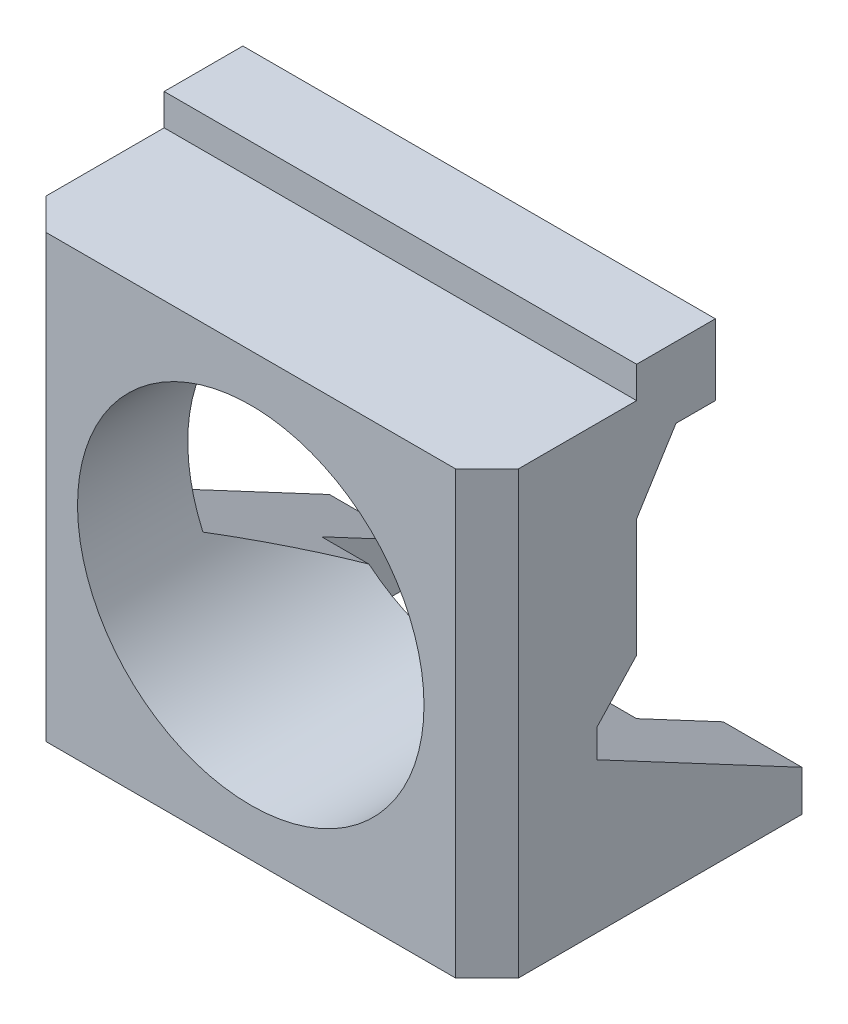
SolidWorks part; units mm, degrees
ref_plane "Front Plane" through (0, 0, 0) normal (0, 0, 1) x (1, 0, 0)
ref_plane "Top Plane" through (0, 0, 0) normal (0, 1, 0) x (1, 0, 0)
ref_plane "Right Plane" through (0, 0, 0) normal (1, 0, 0) x (0, 0, -1)
sketch "Sketch1" plane through (0, 0, 0) normal (0, 0, 1) x (1, 0, 0)
  line L1 (-15, 14) -> (15, 14)
  line L2 (-15, 14) -> (-15, -14)
  line L3 (-15, -14) -> (15, -14)
  line L4 (15, 14) -> (15, -14)
  line L5 (-15, 14) -> (15, -14) construction
  line L6 (-15, -14) -> (15, 14) construction
  circle A0 centre (0, 0) radius 11
  dimension "D1" = 22
  dimension "D2" = 30
  dimension "D3" = 28
extrude "Boss-Extrude1" add sketch "Sketch1" along normal blind 7
sketch "Sketch2" plane through (0, 0, 0) normal (0, 0, -1) x (-1, 0, 0)
  line L0 (0, 0) -> (0, -50000) construction
  line L1 (-15, -14) -> (-10, -14)
  line L2 (-15, -14) -> (-15, -11.5)
  line L3 (-15, -11.5) -> (-10, -11.5)
  line L4 (-10, -14) -> (-10, -11.5)
  line L5 (15, -11.5) -> (10, -11.5)
  line L6 (10, -14) -> (10, -11.5)
  line L7 (15, -14) -> (10, -14)
  line L8 (15, -14) -> (15, -11.5)
  dimension "D1" = 2.5
  dimension "D2" = 5
extrude "Boss-Extrude2" add sketch "Sketch2" along normal blind 13 contours L5 L6 L7 L8 | L2 L3 L4 L1
chamfer "Chamfer2" distance 2 angle 45 2 edges at (-10, -12.75, 0) (10, -12.75, 0)
sketch "Sketch5" plane through (0, -14, 0) normal (0, -1, 0) x (1, 0, 0)
  line L0 (-10, -7.5) -> (10, -7.5)
  line L1 (-10, -13) -> (-10, -2) construction
  line L2 (10, -13) -> (10, -2) construction
  line L3 (10, -7.5) -> (10, -2)
  line L4 (10, -2) -> (8, 0)
  line L5 (8, 0) -> (-8, 0)
  line L6 (-8, 0) -> (-10, -2)
  line L7 (-10, -2) -> (-10, -7.5)
  line M5 (-10, -13) -> (-10, -2)
  line M6 (-10, -2) -> (-8, 0)
  line M7 (-8, 0) -> (8, 0)
  line M8 (8, 0) -> (10, -2)
  line M9 (10, -2) -> (10, -13)
extrude "Boss-Extrude6" add sketch "Sketch5" against normal up to surface (2.5 mm away) contours L0 M5 M9 M8 M7 M6 region at (0, -14, -3.8345) up to face at (11.6, -11.5, -5.6)
chamfer "Chamfer3" distance 2 angle 45 1 edges at (15, 0, 7)
chamfer "Chamfer4" distance 2 angle 45 1 edges at (-15, 0, 7)
sketch "Sketch4" plane through (0, 0, 0) normal (0, 0, -1) x (-1, 0, 0)
  line L1 (-15, -11.5) -> (-15, 14) construction
  line L2 (-15, 14) -> (15, 14) construction
  line L3 (15, 14) -> (15, -11.5) construction
  line L8 (0, 0) -> (0, 50000) construction
  line L14 (-15, 0) -> (15, 11.5)
  line L15 (15, 11.5) -> (15, 14)
  line L16 (15, 14) -> (-15, 14)
  line L18 (-15, 14) -> (-15, 0)
  line L19 (-15, 14) -> (-15, -14) construction
  point P8 (-15, 0)
  dimension "D1" = 2.5
extrude "Boss-Extrude4" add sketch "Sketch4" along normal blind 2.5
chamfer "Chamfer6" distance 2.5 2 edges at (12.9432, 0.7884, 0) (-11.0214, 9.9749, 0)
chamfer "Chamfer7" distance 7 angle 62 1 edges at (0, -11.5, 0) first distance on face at (-0.4851, -4.0745, 0)
sketch "Sketch7" plane through (0, -14, 0) normal (0, -1, 0) x (1, 0, 0)
  circle A0 centre (11, 2.5) radius 2 construction
  circle A1 centre (-11, 2.5) radius 2 construction
  circle A2 centre (11, 2.5) radius 2 construction
  circle A3 centre (-11, 2.5) radius 2 construction
  circle A4 centre (-11, 2.5) radius 1.5
  circle A5 centre (11, 2.5) radius 1.5
  dimension "D1" = 3
  dimension "D2" = 3
extrude "Cut-Extrude2" cut sketch "Sketch7" against normal blind 6.4
sketch "Sketch8" plane through (0, 14, 0) normal (0, 1, 0) x (1, 0, 0)
  line L0 (-15, 2.5) -> (15, 2.5)
  line L1 (-15, -5) -> (-15, 2.5) construction
  line L2 (15, 2.5) -> (15, 7.5)
  line L3 (15, 7.5) -> (-15, 7.5)
  line L4 (-15, 7.5) -> (-15, 2.5)
  line L5 (15, -5) -> (15, 2.5) construction
  line L6 (-15, 2.5) -> (15, 2.5) construction
  dimension "D1" = 5
extrude "Boss-Extrude7" add sketch "Sketch8" along normal up to surface (4.5 mm away) from offset 2.5 offset against normal yes
chamfer "Chamfer8" distance 2.5 angle 58 1 edges at (0, 11.5, -2.5) first distance on face at (0, 11.5, -5)
